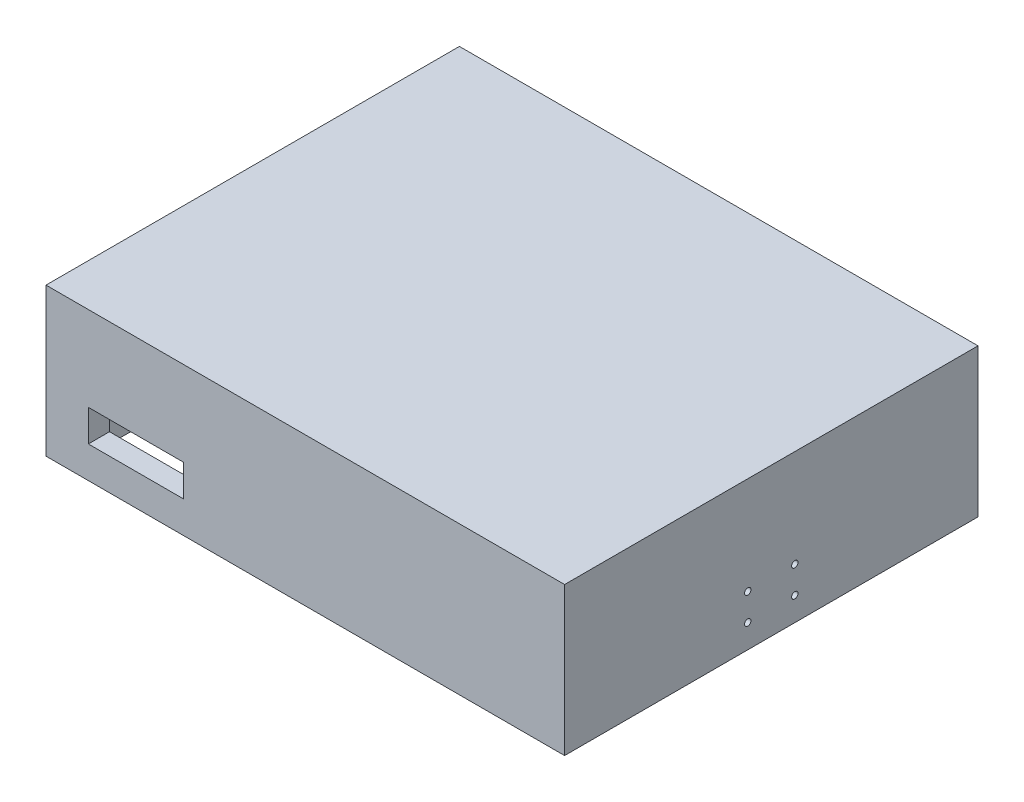
SolidWorks part; units mm, degrees
ref_plane "Front Plane" through (0, 0, 0) normal (0, 0, 1) x (1, 0, 0)
ref_plane "Top Plane" through (0, 0, 0) normal (0, 1, 0) x (1, 0, 0)
ref_plane "Right Plane" through (0, 0, 0) normal (1, 0, 0) x (0, 0, -1)
sketch "Sketch1" plane through (0, 0, 0) normal (0, 1, 0) x (1, 0, 0)
  line L0 (0, 97.65) -> (0, -97.65) construction
  line L1 (122.5, 0) -> (-128.0777, 0) construction
  line L2 (-122.5, 97.65) -> (122.5, 97.65)
  line L3 (122.5, 97.65) -> (122.5, -97.65)
  line L4 (122.5, -97.65) -> (-122.5, -97.65)
  line L5 (-122.5, -97.65) -> (-122.5, 97.65)
  point P7 (0, 97.65)
  point P10 (-122.5, 0)
  dimension "D1" = 245
  dimension "D2" = 195.3
extrude "Boss-Extrude1" add sketch "Sketch1" along normal blind 70
sketch "Sketch2" plane through (0, 0, 0) normal (0, -1, 0) x (1, 0, 0)
  line L0 (-122.5, -97.65) -> (-122.5, 97.65) construction
  line L1 (-112.5, 87.65) -> (112.5, 87.65)
  line L2 (-112.5, 87.65) -> (-112.5, -87.65)
  line L3 (-112.5, -87.65) -> (112.5, -87.65)
  line L4 (112.5, 87.65) -> (112.5, -87.65)
  line L5 (122.5, -97.65) -> (-122.5, -97.65) construction
  line L6 (-122.5, 97.65) -> (122.5, 97.65) construction
  line L7 (122.5, 97.65) -> (122.5, -97.65) construction
  dimension "D1" = 10
  dimension "D2" = 10
  dimension "D3" = 10
  dimension "D4" = 10
extrude "Cut-Extrude1" cut sketch "Sketch2" against normal blind 60
sketch "Sketch3" plane through (122.5, 0, 0) normal (1, 0, 0) x (0, 0, -1)
  line L0 (-97.65, 0) -> (97.65, 0) construction
  line L1 (0, 0) -> (0, 70) construction
  line L2 (-97.65, 70) -> (97.65, 70) construction
  circle A0 centre (-11.115, 23.9) radius 1.5
  circle A1 centre (11.11, 23.9001) radius 1.5
  circle A2 centre (-11.115, 11.2) radius 1.5
  circle A3 centre (11.11, 11.2) radius 1.5
  dimension "D1" = 3
  dimension "D2" = 3
  dimension "D3" = 3
  dimension "D4" = 3
  dimension "D7" = 11.2
  dimension "D8" = 12.7
  dimension "D12" = 11.115
  dimension "D5" = 22.225
  dimension "D6" = 22.225
  dimension "D9" = 12.7001
  dimension "D10" = 11.2
  dimension "D11" = 23.9
extrude "Cut-Extrude2" cut sketch "Sketch3" against normal blind 5
sketch "Sketch4" plane through (0, 0, 0) normal (0, -1, 0) x (1, 0, 0)
  line L0 (122.5, -97.65) -> (-122.5, -97.65) construction
  line L1 (-122.5, 97.65) -> (122.5, 97.65) construction
  line L2 (-122.5, -97.65) -> (-122.5, 97.65) construction
  line L3 (122.5, 97.65) -> (122.5, -97.65) construction
  line L4 (-97.65, 92.65) -> (-97.65, -92.65) construction
  line L5 (-97.65, -92.65) -> (107.5, -92.65) construction
  line L6 (107.5, -92.65) -> (107.5, 92.65) construction
  line L7 (107.5, 92.65) -> (-97.65, 92.65) construction
  circle A0 centre (-97.65, 92.65) radius 2.5
  circle A1 centre (-97.65, -92.65) radius 2.5
  circle A2 centre (107.5, -92.65) radius 2.5
  circle A3 centre (107.5, 92.65) radius 2.5
  dimension "D1" = 5
  dimension "D2" = 5
  dimension "D3" = 5
  dimension "D4" = 5
  dimension "D5" = 5
  dimension "D6" = 5
  dimension "D7" = 24.85
  dimension "D8" = 24.85
  dimension "D9" = 15
  dimension "D10" = 5
  dimension "D11" = 15
  dimension "D12" = 5
sketch "Sketch5" plane through (0, 0, 0) normal (0, -1, 0) x (1, 0, 0)
  line L0 (-96.5, 92.65) -> (-96.5, -92.65) construction
  line L3 (107.5, 92.65) -> (-96.5, 92.65) construction
  line L9 (-96.5, -92.65) -> (107.5, -92.65) construction
  line L10 (107.5, 92.65) -> (107.5, -92.65) construction
  line L12 (-122.5, -97.65) -> (-122.5, 97.65) construction
  line L13 (-122.5, 97.65) -> (122.5, 97.65) construction
  line L15 (107.5, -93.65) -> (-96.5, -93.65)
  line L16 (107.5, -93.65) -> (107.5, -91.65)
  line L17 (107.5, -91.65) -> (-96.5, -91.65)
  line L18 (-96.5, -93.65) -> (-96.5, -91.65)
  line L19 (107.5, -93.65) -> (-96.5, -91.65) construction
  line L20 (107.5, -91.65) -> (-96.5, -93.65) construction
  line L21 (107.5, 93.65) -> (-96.5, 93.65)
  line L22 (107.5, 93.65) -> (107.5, 91.65)
  line L23 (107.5, 91.65) -> (-96.5, 91.65)
  line L24 (-96.5, 93.65) -> (-96.5, 91.65)
  line L25 (107.5, 93.65) -> (-96.5, 91.65) construction
  line L26 (107.5, 91.65) -> (-96.5, 93.65) construction
  point P1 (5.5, -92.65)
  point P10 (5.5, 92.65)
  dimension "D1" = 2
  dimension "D2" = 26
  dimension "D3" = 5
  dimension "D4" = 2
extrude "Boss-Extrude3" add sketch "Sketch5" along normal blind 3
sketch "Sketch6" plane through (-122.5, 0, 0) normal (-1, 0, 0) x (0, 0, 1)
  line L0 (-97.65, 70) -> (-97.65, 0) construction
  line L1 (-82.65, 30) -> (-22.65, 30)
  line L2 (-82.65, 30) -> (-82.65, 0)
  line L3 (-82.65, 0) -> (-22.65, 0)
  line L4 (-22.65, 30) -> (-22.65, 0)
  line L5 (-82.65, 30) -> (-22.65, 0) construction
  line L6 (-82.65, 0) -> (-22.65, 30) construction
  line L8 (-97.65, 0) -> (97.65, 0) construction
  point P0 (-52.65, 15)
  point P5 (-52.1142, 29.8785)
  dimension "D1" = 60
  dimension "D2" = 30
  dimension "D3" = 15
extrude "Cut-Extrude3" cut sketch "Sketch6" against normal blind 10
sketch "Sketch7" plane through (0, 0, -97.65) normal (0, 0, -1) x (-1, 0, 0)
  line L1 (82.5, -3) -> (37.5, -3)
  line L2 (82.5, -3) -> (82.5, 11)
  line L3 (82.5, 11) -> (37.5, 11)
  line L4 (37.5, -3) -> (37.5, 11)
  line L5 (122.5, 70) -> (122.5, 0) construction
  line L6 (96.5, -3) -> (-107.5, -3) construction
  dimension "D1" = 40
  dimension "D2" = 45
  dimension "D3" = 14
extrude "Cut-Extrude5" cut sketch "Sketch7" against normal blind 10
sketch "Sketch8" plane through (0, 0, 97.65) normal (0, 0, 1) x (1, 0, 0)
  line L0 (-122.5, 70) -> (-122.5, 0) construction
  line L1 (-102.5, 15) -> (-57.5, 15)
  line L2 (-102.5, 15) -> (-102.5, 30)
  line L3 (-102.5, 30) -> (-57.5, 30)
  line L4 (-57.5, 15) -> (-57.5, 30)
  line L5 (-122.5, 0) -> (122.5, 0) construction
  dimension "D1" = 20
  dimension "D2" = 15
  dimension "D3" = 45
  dimension "D4" = 15
extrude "Cut-Extrude6" cut sketch "Sketch8" against normal blind 10
